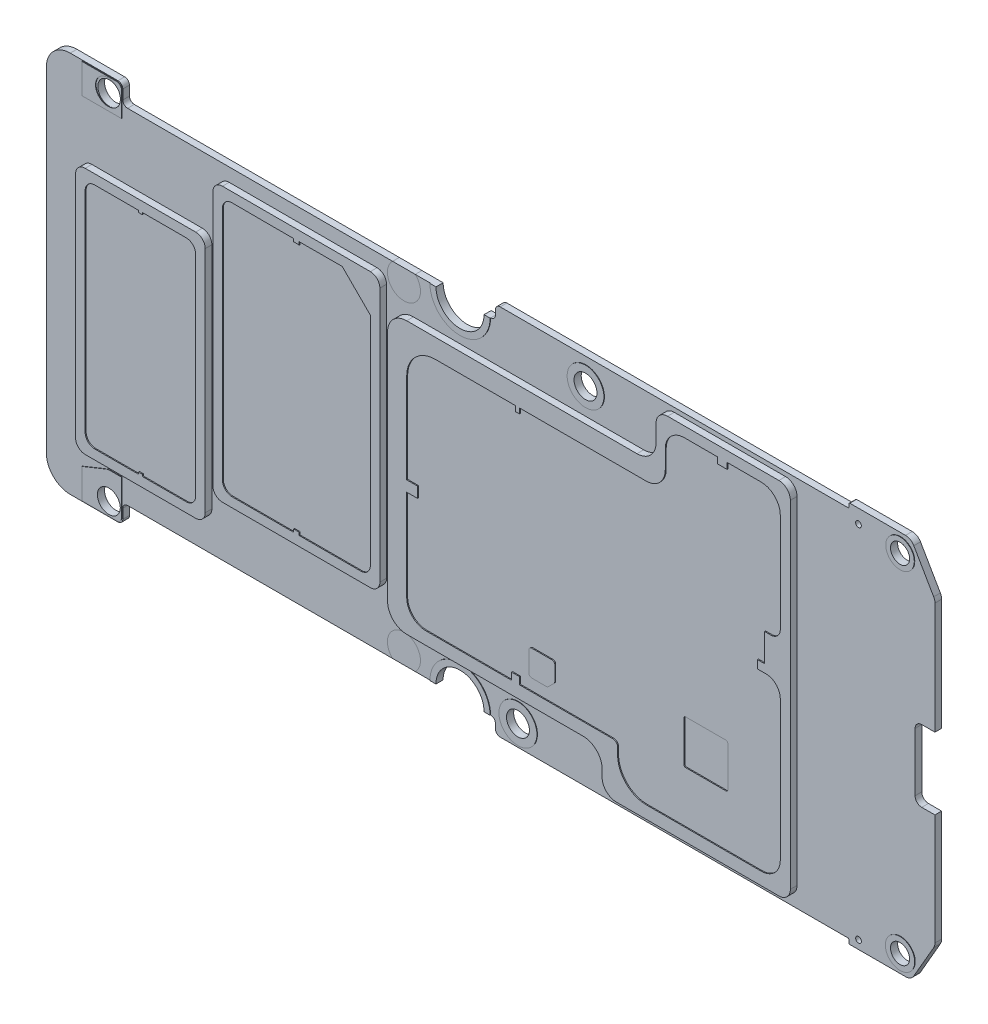
SolidWorks part; units mm, degrees
material "环氧树脂,未充填"
ref_plane "前视基准面" through (0, 0, 0) normal (0, 0, 1) x (1, 0, 0)
ref_plane "上视基准面" through (0, 0, 0) normal (0, 1, 0) x (1, 0, 0)
ref_plane "右视基准面" through (0, 0, 0) normal (1, 0, 0) x (0, 0, -1)
sketch "草图1" plane through (0, 0, 0) normal (0, 0, 1) x (1, 0, 0)
  line L1 (-44.1538, 40.8462) -> (48.8462, 40.8462)
  line L2 (-44.1538, 40.8462) -> (-44.1538, 0.8462)
  line L3 (-44.1538, 0.8462) -> (48.8462, 0.8462)
  line L4 (48.8462, 40.8462) -> (48.8462, 0.8462)
  dimension "D1" = 93
  dimension "D2" = 40
extrude "凸台-拉伸1" add sketch "草图1" along normal blind 0.7
sketch "草图2" plane through (0, 0, 0.7) normal (0, 0, 1) x (1, 0, 0)
  line L0 (-44.1538, 3.3462) -> (-44.1538, 38.3462)
  line L1 (48.8462, 40.8462) -> (-44.1538, 40.8462) construction
  line L2 (-44.1538, 40.8462) -> (-44.1538, 0.8462) construction
  line L3 (-41.6538, 40.8462) -> (-36.6538, 40.8462)
  line L4 (-36.1538, 40.3462) -> (-36.1538, 39.3462)
  line L5 (-41.6538, 0.8462) -> (-38.1538, 0.8462)
  line L6 (-44.1538, 0.8462) -> (48.8462, 0.8462) construction
  line L7 (-35.6538, 38.8462) -> (2.3462, 38.8462)
  line L8 (2.8462, 39.3462) -> (2.8462, 39.8462)
  line L9 (3.3462, 40.3462) -> (39.7462, 40.3462)
  line L10 (48.8462, 0.8462) -> (48.8462, 40.8462) construction
  line L11 (-44.1538, 38.3462) -> (-44.1538, 3.3462)
  line L12 (39.8462, 40.4462) -> (39.8462, 40.7462)
  line L13 (39.9462, 40.8462) -> (46.3462, 40.8462)
  line L14 (48.8462, 38.3462) -> (48.8462, 3.3462)
  line L15 (46.3462, 0.8462) -> (39.9462, 0.8462)
  line L16 (39.8462, 0.9462) -> (39.8462, 1.2462)
  line L17 (39.7462, 1.3462) -> (3.3462, 1.3462)
  line L18 (2.8462, 1.8462) -> (2.8462, 2.3462)
  line L19 (2.3462, 2.8462) -> (-35.6538, 2.8462)
  line L20 (-36.1538, 2.3462) -> (-36.1538, 1.3462)
  line L21 (-36.6538, 0.8462) -> (-44.1538, 0.8462)
  line L22 (48.8462, 38.3462) -> (48.8462, 3.3462)
  arc A0 (-41.6538, 0.8462) -> (-44.1538, 3.3462) centre (-41.6538, 3.3462) cw
  arc A1 (-41.6538, 40.8462) -> (-44.1538, 38.3462) centre (-41.6538, 38.3462) ccw
  arc A2 (3.3462, 1.3462) -> (2.8462, 1.8462) centre (3.3462, 1.8462) cw
  arc A3 (2.8462, 2.3462) -> (2.3462, 2.8462) centre (2.3462, 2.3462) ccw
  arc A4 (-35.6538, 2.8462) -> (-36.1538, 2.3462) centre (-35.6538, 2.3462) ccw
  arc A5 (-36.1538, 1.3462) -> (-36.6538, 0.8462) centre (-36.6538, 1.3462) cw
  arc A6 (2.8462, 39.8462) -> (3.3462, 40.3462) centre (3.3462, 39.8462) cw
  arc A7 (2.8462, 39.3462) -> (2.3462, 38.8462) centre (2.3462, 39.3462) cw
  arc A8 (-36.1538, 39.3462) -> (-35.6538, 38.8462) centre (-35.6538, 39.3462) ccw
  arc A9 (-36.1538, 40.3462) -> (-36.6538, 40.8462) centre (-36.6538, 40.3462) ccw
  arc A10 (48.8462, 3.3462) -> (46.3462, 0.8462) centre (46.3462, 3.3462) cw
  arc A11 (48.8462, 38.3462) -> (46.3462, 40.8462) centre (46.3462, 38.3462) ccw
  arc A12 (39.9462, 0.8462) -> (39.8462, 0.9462) centre (39.9462, 0.9462) cw
  arc A13 (39.8462, 1.2462) -> (39.7462, 1.3462) centre (39.7462, 1.2462) ccw
  arc A14 (39.9462, 40.8462) -> (39.8462, 40.7462) centre (39.9462, 40.7462) ccw
  arc A15 (39.8462, 40.4462) -> (39.7462, 40.3462) centre (39.7462, 40.4462) cw
  point P32 (-44.1538, 40.8462)
  point P41 (-36.1538, 0.8462)
  point P50 (-36.1538, 40.8462)
  point P52 (48.8462, 0.8462)
  point P55 (48.8462, 40.8462)
  point P58 (39.8462, 0.8462)
  point P63 (39.8462, 40.8462)
  line M1 (-44.1538, 40.8462) -> (-44.1538, 0.8462)
  line M2 (-44.1538, 0.8462) -> (48.8462, 0.8462)
  line M3 (48.8462, 0.8462) -> (48.8462, 40.8462)
  line M4 (48.8462, 40.8462) -> (-44.1538, 40.8462)
  dimension "D1" = 2.5
  dimension "D2" = 0.5
  dimension "D3" = 2.5
  dimension "D4" = 0.1
extrude "切除-拉伸2" cut sketch "草图2" against normal blind 0.7 flip side to cut contours L12 A15 L9 A6 L8 A7 L7 A8 L4 A9 A1 A0 A5 L20 A4 L19 A3 L18 A2 L17 A13 L16 A12 A10 A11 A14 M4 M1 M2 M3 region at (2.9882, 20.8462, 0.7)
sketch "草图3" plane through (0, 0, 0.7) normal (0, 0, 1) x (1, 0, 0)
  line L0 (-36.1538, 39.3462) -> (-37.6538, 39.3462)
  line L1 (-40.392, 40.7562) -> (-40.392, 37.6462)
  line L3 (-40.392, 37.6462) -> (-36.242, 37.6462)
  line L4 (-36.242, 37.6462) -> (-36.242, 40.2562)
  line L5 (-36.6538, 40.8462) -> (-41.6538, 40.8462) construction
  line L6 (-40.392, 40.7562) -> (-36.742, 40.7562)
  line L7 (-40.392, 4.0462) -> (-40.392, 0.9362)
  line L8 (-40.392, 4.0462) -> (-37.6538, 5.1451)
  line L10 (-40.392, 0.9362) -> (-36.742, 0.9362)
  line L11 (-40.392, 0.9362) -> (-40.392, 4.0462)
  line L13 (-36.242, 4.0462) -> (-36.242, 1.4362)
  line L14 (-37.6538, 5.1451) -> (-36.242, 5.1451)
  line L15 (-36.242, 5.1451) -> (-36.242, 4.0462)
  circle A0 centre (-37.6538, 39.3462) radius 1.3
  arc A1 (-36.242, 40.2562) -> (-36.742, 40.7562) centre (-36.742, 40.2562) ccw
  arc A2 (-36.742, 0.9362) -> (-36.242, 1.4362) centre (-36.742, 1.4362) ccw
  dimension "D1" = 0.5
  dimension "D3" = 0.5
  dimension "D2" = 0.09
extrude "凸台-拉伸2" add sketch "草图3" along normal blind 0.05 contours L4 A1 L6 L1 L3 A0 | L10 A2 L13 L7 region at (-36.2939, 38.4962, 0.7) region at (-38.2137, 2.8829, 0.7)
sketch "草图4" plane through (0, 0, 0.75) normal (0, 0, 1) x (1, 0, 0)
  circle A0 centre (-37.5652, 39.2718) radius 1.2
  circle A1 centre (-37.5652, 2.2975) radius 1.2
extrude "切除-拉伸3" cut sketch "草图4" against normal through all
sketch "草图6" plane through (0, 0, 0.7) normal (0, 0, 1) x (1, 0, 0)
  line L1 (-39.392, 31.8895) -> (-27.8273, 31.8895)
  line L2 (-40.392, 30.8895) -> (-40.392, 6.9464)
  line L3 (-39.392, 5.9464) -> (-27.8273, 5.9464)
  line L4 (-26.8273, 30.8895) -> (-26.8273, 6.9464)
  line L5 (-25.026, 37.4487) -> (-9.547, 37.4487)
  line L6 (-26.026, 36.4487) -> (-26.026, 9.8011)
  line L7 (-25.026, 8.8011) -> (-9.547, 8.8011)
  line L8 (-8.547, 36.4487) -> (-8.547, 9.8011)
  arc A0 (-8.547, 36.4487) -> (-9.547, 37.4487) centre (-9.547, 36.4487) ccw
  arc A1 (-8.547, 9.8011) -> (-9.547, 8.8011) centre (-9.547, 9.8011) cw
  arc A2 (-25.026, 8.8011) -> (-26.026, 9.8011) centre (-25.026, 9.8011) cw
  arc A3 (-26.026, 36.4487) -> (-25.026, 37.4487) centre (-25.026, 36.4487) cw
  arc A4 (-26.8273, 30.8895) -> (-27.8273, 31.8895) centre (-27.8273, 30.8895) ccw
  arc A5 (-26.8273, 6.9464) -> (-27.8273, 5.9464) centre (-27.8273, 6.9464) cw
  arc A6 (-39.392, 5.9464) -> (-40.392, 6.9464) centre (-39.392, 6.9464) cw
  arc A7 (-39.392, 31.8895) -> (-40.392, 30.8895) centre (-39.392, 30.8895) ccw
  dimension "D1" = 1
extrude "凸台-拉伸3" add sketch "草图6" along normal blind 0.7
sketch "草图7" plane through (0, 0, 1.4) normal (0, 0, 1) x (1, 0, 0)
  line L0 (-33.8097, 30.8744) -> (-38.392, 30.8744)
  line L1 (-38.392, 30.8744) -> (-33.8097, 30.8744)
  line L2 (-27.8273, 29.8744) -> (-27.8273, 7.9464)
  line L3 (-28.8273, 6.9464) -> (-33.4097, 6.9464)
  line L4 (-39.392, 7.9464) -> (-39.392, 29.8744)
  line L5 (-27.8273, 31.8895) -> (-39.392, 31.8895) construction
  line L6 (-33.4097, 30.8744) -> (-33.4097, 30.6744)
  line L7 (-33.4097, 30.6744) -> (-33.8097, 30.6744)
  line L8 (-33.8097, 30.6744) -> (-33.8097, 30.8744)
  line L9 (-33.4097, 30.8744) -> (-28.8273, 30.8744)
  line L10 (-33.4097, 6.9464) -> (-33.4097, 7.1464)
  line L11 (-33.4097, 7.1464) -> (-33.8097, 7.1464)
  line L12 (-33.8097, 7.1464) -> (-33.8097, 6.9464)
  line L13 (-15.2085, 36.4378) -> (-14.9474, 36.4383)
  line L14 (-33.8097, 6.9464) -> (-38.392, 6.9464)
  line L15 (-12.4872, 36.4431) -> (-9.547, 33.5028)
  line L16 (-19.868, 36.4287) -> (-24.0221, 36.4449)
  line L17 (-25.026, 35.4449) -> (-25.026, 10.8011)
  line L18 (-24.026, 9.8011) -> (-17.5865, 9.8011)
  line L19 (-9.547, 10.8011) -> (-9.547, 35.4468)
  line L20 (-10.5489, 36.4468) -> (-16.9865, 36.4343)
  line L23 (-17.5865, 36.4332) -> (-17.5865, 36.1332)
  line L24 (-17.5865, 36.1332) -> (-16.9865, 36.1332)
  line L25 (-16.9865, 36.1332) -> (-16.9865, 36.4343)
  line L26 (-16.9865, 9.8011) -> (-10.547, 9.8011)
  line L27 (-17.5865, 36.4332) -> (-19.868, 36.4287)
  line L28 (-16.9865, 9.8011) -> (-16.9865, 10.101)
  line L29 (-16.9865, 10.101) -> (-17.5865, 10.101)
  line L30 (-17.5865, 9.8011) -> (-17.5865, 10.101)
  arc A0 (-27.8273, 29.8744) -> (-28.8273, 30.8744) centre (-28.8273, 29.8744) ccw
  arc A1 (-28.8273, 6.9464) -> (-27.8273, 7.9464) centre (-28.8273, 7.9464) ccw
  arc A2 (-38.392, 6.9464) -> (-39.392, 7.9464) centre (-38.392, 7.9464) cw
  arc A3 (-38.392, 30.8744) -> (-39.392, 29.8744) centre (-38.392, 29.8744) ccw
  arc A4 (-24.026, 9.8011) -> (-25.026, 10.8011) centre (-24.026, 10.8011) cw
  arc A5 (-10.547, 9.8011) -> (-9.547, 10.8011) centre (-10.547, 10.8011) ccw
  arc A6 (-9.547, 35.4468) -> (-10.5489, 36.4468) centre (-10.547, 35.4468) ccw
  arc A7 (-25.026, 35.4449) -> (-24.0221, 36.4449) centre (-24.026, 35.4449) cw
  point P11 (-27.8273, 6.9464)
  point P14 (-39.392, 6.9464)
  point P29 (-25.026, 9.8011)
  point P40 (-9.547, 9.8011)
  point P43 (-9.547, 36.4487)
  point P46 (-25.026, 36.4487)
  dimension "D1" = 1
  dimension "D3" = 1
  dimension "D2" = 1.0151
extrude "切除-拉伸4" cut sketch "草图7" against normal blind 0.7 contours L0 A3 L4 A2 L14 L12 L11 L10 L3 A1 L2 A0 L9 L6 L7 L8 | A7 L17 A4 L18 L30 L29 L28 L26 A5 L19 A6 L20 L13 L25 L24 L23 L27 L16 region at (-33.6097, 18.9104, 1.4) region at (-17.3541, 22.9954, 1.4)
ref_plane "基准面1" through (0, 0, 0.7) normal (0, 0, 1) x (1, 0, 0)
sketch "草图8" plane through (0, 0, 0.7) normal (0, 0, 1) x (1, 0, 0)
  line L0 (-39.0991, 31.5966) -> (-28.0238, 31.5966)
  line L1 (-40.0991, 30.5966) -> (-40.0991, 7.1828)
  line L2 (-39.0991, 6.1828) -> (-28.0238, 6.1828)
  line L3 (-27.0238, 7.1828) -> (-27.0238, 30.5966)
  line L4 (-24.7331, 37.237) -> (-9.8414, 37.237)
  line L5 (-25.7331, 36.237) -> (-25.7331, 10.094)
  line L6 (-24.7331, 9.094) -> (-9.8414, 9.094)
  line L7 (-8.8414, 36.237) -> (-8.8414, 10.094)
  arc A0 (-39.0991, 6.1828) -> (-40.0991, 7.1828) centre (-39.0991, 7.1828) cw
  arc A1 (-27.0238, 7.1828) -> (-28.0238, 6.1828) centre (-28.0238, 7.1828) cw
  arc A2 (-27.0238, 30.5966) -> (-28.0238, 31.5966) centre (-28.0238, 30.5966) ccw
  arc A3 (-40.0991, 30.5966) -> (-39.0991, 31.5966) centre (-39.0991, 30.5966) cw
  arc A4 (-9.8414, 37.237) -> (-8.8414, 36.237) centre (-9.8414, 36.237) cw
  arc A5 (-9.8414, 9.094) -> (-8.8414, 10.094) centre (-9.8414, 10.094) ccw
  arc A6 (-24.7331, 9.094) -> (-25.7331, 10.094) centre (-24.7331, 10.094) cw
  arc A7 (-25.7331, 36.237) -> (-24.7331, 37.237) centre (-24.7331, 36.237) cw
  dimension "D1" = 1
  dimension "D2" = 1
extrude "切除-拉伸5" cut sketch "草图8" along normal blind 0.6
sketch "草图9" plane through (0, 0, 0.7) normal (0, 0, 1) x (1, 0, 0)
  line L0 (-6.7276, 38.8462) -> (-6.7276, 37.5835)
  line L1 (-35.6538, 38.8462) -> (2.3462, 38.8462) construction
  line L2 (2.3462, 2.8462) -> (-35.6538, 2.8462) construction
  circle A0 centre (-6.7276, 37.5835) radius 1.73
  circle A1 centre (-6.7276, 4.0995) radius 1.73
  circle A2 centre (-0.8113, 38.8462) radius 2.5151
  circle A3 centre (-0.8113, 2.8462) radius 2.52
extrude "切除-拉伸6" cut sketch "草图9" against normal through all contours A0 | A1 | A2 | A3 region at (-8.4087, 37.5835, 0.7) region at (-6.7276, 4.0995, 0.7) region at (-0.8113, 38.8462, 0.7) region at (-0.8113, 2.8462, 0.7)
sketch "草图11" plane through (0, 0, 0.7) normal (0, 0, 1) x (1, 0, 0)
  line L0 (-3.9612, 38.8462) -> (-3.3264, 38.8462)
  line L1 (-5.545, 38.8462) -> (-3.3264, 38.8462) construction
  line L2 (-3.3313, 2.8462) -> (-3.9612, 2.8462)
  line L3 (1.7039, 38.8462) -> (2.3462, 38.8462)
  line L4 (-3.3313, 2.8462) -> (-5.5352, 2.8462) construction
  line L5 (-3.9612, 2.8462) -> (-3.3313, 2.8462)
  line L6 (1.7087, 2.8462) -> (2.3462, 2.8462)
  arc A0 (-3.9612, 38.8462) -> (2.3387, 38.8462) centre (-0.8113, 38.8462) ccw
  arc A1 (2.3387, 2.8462) -> (-3.9612, 2.8462) centre (-0.8113, 2.8462) ccw
  arc A2 (-3.3264, 38.8462) -> (1.7039, 38.8462) centre (-0.8113, 38.8462) ccw
  arc A3 (1.7087, 2.8462) -> (-3.3313, 2.8462) centre (-0.8113, 2.8462) ccw
extrude "凸台-拉伸4" add sketch "草图11" along normal blind 0.05 contours A3 L6 A1 L2 | A2 L0 A0 L3 region at (-3.6438, 38.7757, 0.7) region at (-3.6462, 2.9166, 0.7)
sketch "草图12" plane through (0, 0, 0.7) normal (0, 0, 1) x (1, 0, 0)
  line L0 (-5.7402, 34.8947) -> (18.3612, 34.8947)
  line L1 (20.3612, 36.8947) -> (20.3612, 38.6947)
  line L2 (21.5612, 39.8947) -> (33.2119, 39.8947)
  line L3 (34.4119, 38.6947) -> (34.4119, 3.438)
  line L4 (33.2119, 2.238) -> (16.2153, 2.238)
  line L5 (14.7153, 3.738) -> (14.7153, 4.4725)
  line L6 (12.7153, 6.4725) -> (-5.7402, 6.4725)
  line L7 (-7.7402, 8.4725) -> (-7.7402, 32.8947)
  arc A0 (-5.7402, 6.4725) -> (-7.7402, 8.4725) centre (-5.7402, 8.4725) cw
  arc A1 (-5.7402, 34.8947) -> (-7.7402, 32.8947) centre (-5.7402, 32.8947) ccw
  arc A2 (14.7153, 4.4725) -> (12.7153, 6.4725) centre (12.7153, 4.4725) ccw
  arc A3 (20.3612, 36.8947) -> (18.3612, 34.8947) centre (18.3612, 36.8947) cw
  arc A4 (33.2119, 2.238) -> (34.4119, 3.438) centre (33.2119, 3.438) ccw
  arc A5 (34.4119, 38.6947) -> (33.2119, 39.8947) centre (33.2119, 38.6947) ccw
  arc A6 (21.5612, 39.8947) -> (20.3612, 38.6947) centre (21.5612, 38.6947) ccw
  arc A7 (16.2153, 2.238) -> (14.7153, 3.738) centre (16.2153, 3.738) cw
  dimension "D1" = 2
  dimension "D2" = 2
  dimension "D3" = 1.2
  dimension "D4" = 1.5
extrude "凸台-拉伸5" add sketch "草图12" along normal blind 0.7
sketch "草图14" plane through (0, 0, 1.4) normal (0, 0, 1) x (1, 0, 0)
  line L0 (-2.7402, 32.8947) -> (5.6481, 32.8947)
  line L1 (21.3198, 34.8947) -> (21.3198, 36.8233)
  line L2 (23.3198, 38.8233) -> (26.7828, 38.8233)
  line L3 (33.3596, 36.8233) -> (33.3596, 26.4576)
  line L4 (31.3596, 3.5527) -> (19.3342, 3.5527)
  line L5 (16.3342, 6.5527) -> (16.3342, 7.2958)
  line L6 (15.8342, 7.7958) -> (6.047, 7.7958)
  line L7 (-5.7402, 9.7958) -> (-5.7402, 19.3582)
  line L8 (33.3596, 20.1919) -> (33.3596, 5.5527)
  line L9 (-5.7402, 20.472) -> (-4.616, 20.472)
  line L10 (6.047, 32.8947) -> (19.3198, 32.8947)
  line L11 (-5.7402, 19.3582) -> (-4.616, 19.3582)
  line L12 (-4.616, 20.472) -> (-4.616, 19.3582)
  line L13 (-5.7402, 20.472) -> (-5.7402, 29.8947)
  line L14 (5.2492, 7.7958) -> (5.2492, 8.5383)
  line L15 (5.2492, 8.5383) -> (6.047, 8.5383)
  line L16 (6.047, 7.7958) -> (6.047, 8.5383)
  line L17 (27.7905, 38.8233) -> (31.3596, 38.8233)
  line L18 (5.6481, 32.8947) -> (5.6481, 32.3526)
  line L19 (5.6481, 32.3526) -> (6.047, 32.3526)
  line L20 (6.047, 32.8947) -> (6.047, 32.3526)
  line L22 (26.7828, 38.8233) -> (26.7828, 38.1869)
  line L23 (26.7828, 38.1869) -> (27.7905, 38.1869)
  line L24 (27.7905, 38.8233) -> (27.7905, 38.1869)
  line L25 (32.3596, 25.4576) -> (31.7154, 25.4576)
  line L26 (5.2492, 7.7958) -> (-3.7402, 7.7958)
  line L27 (31.8596, 21.6919) -> (31.7154, 21.6919)
  line L28 (31.7154, 25.4576) -> (31.7154, 22.5405)
  line L29 (31.7154, 22.5405) -> (30.9729, 22.5405)
  line L31 (31.7154, 21.6919) -> (30.9729, 21.6919)
  line L32 (30.9729, 22.5405) -> (30.9729, 21.6919)
  arc A0 (19.3342, 3.5527) -> (16.3342, 6.5527) centre (19.3342, 6.5527) cw
  arc A1 (-2.7402, 32.8947) -> (-5.7402, 29.8947) centre (-2.7402, 29.8947) ccw
  arc A2 (31.3596, 3.5527) -> (33.3596, 5.5527) centre (31.3596, 5.5527) ccw
  arc A3 (33.3596, 36.8233) -> (31.3596, 38.8233) centre (31.3596, 36.8233) ccw
  arc A4 (23.3198, 38.8233) -> (21.3198, 36.8233) centre (23.3198, 36.8233) ccw
  arc A5 (19.3198, 32.8947) -> (21.3198, 34.8947) centre (19.3198, 34.8947) ccw
  arc A6 (-3.7402, 7.7958) -> (-5.7402, 9.7958) centre (-3.7402, 9.7958) cw
  arc A7 (16.3342, 7.2958) -> (15.8342, 7.7958) centre (15.8342, 7.2958) ccw
  arc A8 (31.8596, 21.6919) -> (33.3596, 20.1919) centre (31.8596, 20.1919) cw
  arc A9 (33.3596, 26.4576) -> (32.3596, 25.4576) centre (32.3596, 26.4576) cw
  point P13 (-5.7402, 32.8947)
  dimension "D1" = 3
  dimension "D2" = 2
  dimension "D3" = 0.5
  dimension "D4" = 1.5
  dimension "D5" = 1
extrude "切除-拉伸8" cut sketch "草图14" against normal blind 0.7
sketch "草图15" plane through (0, 0, 0.7) normal (0, 0, 1) x (1, 0, 0)
  line L0 (-6.1544, 34.3089) -> (19.7116, 34.3089)
  line L1 (20.7116, 35.3089) -> (20.7116, 38.4831)
  line L3 (21.7116, 39.4831) -> (33.1582, 39.4831)
  line L5 (34.1582, 38.4831) -> (34.1582, 3.7582)
  line L7 (33.1582, 2.7582) -> (16.1151, 2.7582)
  line L8 (16.2572, 2.7582) -> (15.1151, 3.9004)
  line L9 (15.1151, 3.7582) -> (15.1151, 5.6977)
  line L10 (14.1352, 6.6975) -> (-6.1745, 7.1058)
  line L12 (-7.1544, 8.1056) -> (-7.1544, 33.3089)
  line L13 (-7.1544, 33.4042) -> (-7.1496, 33.4073)
  arc A0 (34.1582, 38.4831) -> (33.1582, 39.4831) centre (33.1582, 38.4831) ccw
  arc A1 (21.7116, 39.4831) -> (20.7116, 38.4831) centre (21.7116, 38.4831) ccw
  arc A2 (34.1582, 3.7582) -> (33.1582, 2.7582) centre (33.1582, 3.7582) cw
  arc A3 (16.1151, 2.7582) -> (15.1151, 3.7582) centre (16.1151, 3.7582) cw
  arc A4 (-6.1745, 7.1058) -> (-7.1544, 8.1056) centre (-6.1544, 8.1056) cw
  arc A5 (-7.1544, 33.3089) -> (-6.1544, 34.3089) centre (-6.1544, 33.3089) cw
  arc A6 (15.1151, 5.6977) -> (14.1352, 6.6975) centre (14.1151, 5.6977) ccw
  arc A7 (19.7116, 34.3089) -> (20.7116, 35.3089) centre (19.7116, 35.3089) ccw
  dimension "D1" = 1
  dimension "D2" = 1
extrude "切除-拉伸9" cut sketch "草图15" along normal blind 0.6 contours L0 A7 L1 A1 L3 A0 L5 A2 L7 A3 L9 A6 L10 A4 L12 A5
sketch "草图16" plane through (0, 0, 0.7) normal (0, 0, 1) x (1, 0, 0)
  line L0 (48.8462, 20.8462) -> (48.8462, 24.5462)
  line L1 (48.8462, 3.3462) -> (48.8462, 38.3462) construction
  line L2 (48.8462, 24.5462) -> (47.4648, 24.5462)
  line L3 (46.7648, 23.8462) -> (46.7648, 17.7462)
  line L4 (47.4648, 17.0462) -> (48.8462, 17.0462)
  line L5 (48.8462, 17.0462) -> (48.8462, 20.8462)
  arc A0 (47.4648, 17.0462) -> (46.7648, 17.7462) centre (47.4648, 17.7462) cw
  arc A1 (47.4648, 24.5462) -> (46.7648, 23.8462) centre (47.4648, 23.8462) ccw
  dimension "D3" = 0.7
  dimension "D1" = 3.8
  dimension "D2" = 7.5
extrude "切除-拉伸10" cut sketch "草图16" against normal through all
sketch "草图17" plane through (0, 0, 0.7) normal (0, 0, 1) x (1, 0, 0)
  circle A0 centre (5.2518, 3.5471) radius 1.9908
  circle A1 centre (12.3251, 37.6544) radius 1.9246
extrude "凸台-拉伸6" add sketch "草图17" along normal blind 0.05
sketch "草图18" plane through (0, 0, 0.75) normal (0, 0, 1) x (1, 0, 0)
  line L0 (48.8462, 36.2481) -> (48.8462, 40.8462)
  line L2 (46.6348, 40.3462) -> (48.7122, 36.7481)
  line L3 (48.8462, 24.5462) -> (48.8462, 38.3462) construction
  line L4 (45.9775, 40.8462) -> (45.7688, 40.8462)
  line L6 (46.6348, 1.3462) -> (48.7122, 4.9442)
  line L7 (48.8462, 3.3462) -> (48.8462, 17.0462) construction
  line L9 (45.7688, 0.8462) -> (48.8462, 0.8462)
  line L10 (48.8462, 0.8462) -> (48.8462, 5.4442)
  line L11 (48.8462, 40.8462) -> (45.9775, 40.8462)
  circle A0 centre (12.3251, 37.6544) radius 1.2
  circle A1 centre (5.2518, 3.5471) radius 1.2
  arc A2 (48.7122, 4.9442) -> (48.8462, 5.4442) centre (47.8462, 5.4442) ccw
  arc A3 (46.6348, 1.3462) -> (45.7688, 0.8462) centre (45.7688, 1.8462) cw
  arc A4 (45.7688, 40.8462) -> (46.6348, 40.3462) centre (45.7688, 39.8462) cw
  arc A5 (48.7122, 36.7481) -> (48.8462, 36.2481) centre (47.8462, 36.2481) cw
  point P24 (48.8462, 5.1763)
  point P27 (46.3462, 0.8462)
  point P30 (46.3462, 40.8462)
  point P33 (48.8462, 36.516)
  dimension "D1" = 1
extrude "切除-拉伸11" cut sketch "草图18" against normal through all
sketch "草图19" plane through (0, 0, 0.7) normal (0, 0, 1) x (1, 0, 0)
  circle A0 centre (45.2417, 38.9852) radius 1.4926
  circle A1 centre (45.2417, 2.7113) radius 1.5385
  circle A2 centre (40.8433, 39.3992) radius 0.3
  circle A3 centre (40.8433, 1.7281) radius 0.3
extrude "凸台-拉伸7" add sketch "草图19" along normal blind 0.05
sketch "草图20" plane through (0, 0, 0.75) normal (0, 0, 1) x (1, 0, 0)
  circle A0 centre (45.2417, 38.9852) radius 1
  circle A1 centre (45.2417, 2.7113) radius 1
  circle A2 centre (40.8433, 39.3992) radius 0.3
  circle A3 centre (40.8433, 1.7281) radius 0.3
extrude "切除-拉伸12" cut sketch "草图20" against normal through all
sketch "草图21" plane through (0, 0, 0.7) normal (0, 0, 1) x (1, 0, 0)
  line L1 (22.769, 12.8877) -> (26.969, 12.8877)
  line L2 (22.569, 12.6877) -> (22.569, 8.4877)
  line L3 (22.769, 8.2877) -> (26.969, 8.2877)
  line L4 (27.169, 12.6877) -> (27.169, 8.4877)
  arc A0 (27.169, 12.6877) -> (26.969, 12.8877) centre (26.969, 12.6877) ccw
  arc A1 (22.769, 8.2877) -> (22.569, 8.4877) centre (22.769, 8.4877) cw
  arc A2 (26.969, 8.2877) -> (27.169, 8.4877) centre (26.969, 8.4877) ccw
  arc A3 (22.769, 12.8877) -> (22.569, 12.6877) centre (22.769, 12.6877) ccw
  point P6 (27.169, 12.8877)
  point P9 (22.569, 8.2877)
  point P14 (22.569, 12.8877)
  dimension "D3" = 0.2
  dimension "D1" = 4.6
  dimension "D2" = 4.6
extrude "切除-拉伸13" cut sketch "草图21" against normal blind 0.1
sketch "草图22" plane through (0, 0, 0.7) normal (0, 0, 1) x (1, 0, 0)
  line L0 (6.4523, 10.8601) -> (6.4523, 8.7533)
  line L1 (6.7523, 8.4533) -> (8.2699, 8.4533)
  line L2 (8.482, 8.5412) -> (9.0708, 9.13)
  line L3 (9.1586, 9.3421) -> (9.1586, 10.8601)
  line L4 (8.8586, 11.1601) -> (6.7523, 11.1601)
  arc A0 (8.8586, 11.1601) -> (9.1586, 10.8601) centre (8.8586, 10.8601) cw
  arc A1 (9.1586, 9.3421) -> (9.0708, 9.13) centre (8.8586, 9.3421) cw
  arc A2 (8.482, 8.5412) -> (8.2699, 8.4533) centre (8.2699, 8.7533) cw
  arc A3 (6.7523, 8.4533) -> (6.4523, 8.7533) centre (6.7523, 8.7533) cw
  arc A4 (6.4523, 10.8601) -> (6.7523, 11.1601) centre (6.7523, 10.8601) cw
  dimension "D1" = 0.3
extrude "凸台-拉伸8" add sketch "草图22" along normal blind 0.1
sketch "草图23" plane through (0, 0, 0.7) normal (0, 0, 1) x (1, 0, 0)
  line L0 (-7.9103, 38.8462) -> (-5.545, 38.8462)
  line L1 (-7.9201, 2.8462) -> (-5.5352, 2.8462)
  arc A0 (-5.5352, 2.8462) -> (-7.9201, 2.8462) centre (-6.7276, 4.0995) ccw
  arc A1 (-7.9103, 38.8462) -> (-5.545, 38.8462) centre (-6.7276, 37.5835) ccw
extrude "凸台-拉伸9" add sketch "草图23" against normal up to surface (0.7 mm away) separate body up to face at (46.2417, 2.7113, 0)
